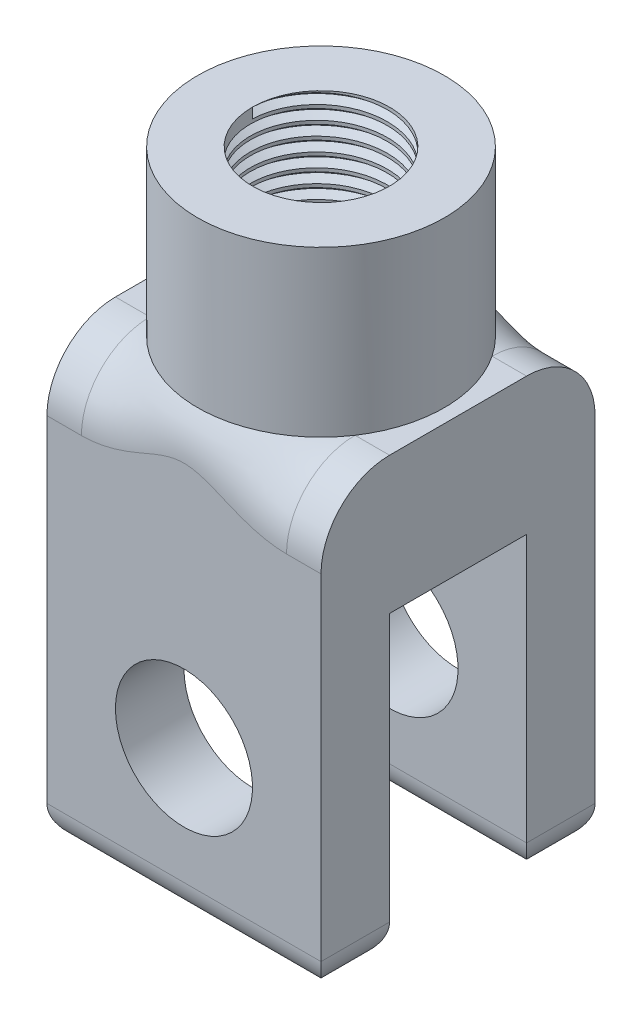
SolidWorks part; units mm, degrees
ref_plane "Front Plane" through (0, 0, 0) normal (0, 0, 1) x (1, 0, 0)
ref_plane "Top Plane" through (0, 0, 0) normal (0, 1, 0) x (1, 0, 0)
ref_plane "Right Plane" through (0, 0, 0) normal (1, 0, 0) x (0, 0, -1)
sketch "Sketch1" plane through (0, 0, 0) normal (0, 0, 1) x (1, 0, 0)
  line L1 (-10, 16) -> (10, 16)
  line L2 (-10, 16) -> (-10, -16)
  line L3 (-10, -16) -> (10, -16)
  line L4 (10, 16) -> (10, -16)
  line L5 (-10, 16) -> (10, -16) construction
  line L6 (-10, -16) -> (10, 16) construction
  point P0 (0, 0)
  dimension "D1" = 20
  dimension "D2" = 32
extrude "Boss-Extrude1" add sketch "Sketch1" along normal blind 20
sketch "Sketch2" plane through (0, 16, 0) normal (0, 1, 0) x (1, 0, 0)
  line L0 (0, 0) -> (0, -20) construction
  line L1 (10, -20) -> (-10, -20) construction
  line L2 (-10, -10) -> (10, -10) construction
  line L3 (-10, -20) -> (-10, 0) construction
  line L4 (10, -20) -> (10, 0) construction
  circle A0 centre (0, -10) radius 9
  dimension "D1" = 18
extrude "Boss-Extrude2" add sketch "Sketch2" along normal blind 12
fillet "Fillet3" radius 5 2 edges at (0, 16, 20) (0, 16, 0)
sketch "Sketch3" plane through (-10, 0, 0) normal (-1, 0, 0) x (0, 0, 1)
  line L0 (20, -16) -> (0, -16) construction
  line L1 (5, -38) -> (15, -38)
  line L2 (5, -38) -> (5, 6)
  line L3 (5, 6) -> (15, 6)
  line L4 (15, -38) -> (15, 6)
  line L5 (5, -38) -> (15, 6) construction
  line L6 (5, 6) -> (15, -38) construction
  point P0 (10, -16)
  dimension "D1" = 10
  dimension "D2" = 44
extrude "Cut-Extrude1" cut sketch "Sketch3" against normal blind 20
fillet "Fillet4" radius 2.5 8 edges at (0, -16, 20) (-10, -16, 17.5) (0, -16, 0) (-10, -16, 2.5) (0, -16, 15) (0, -16, 5) (10, -16, 17.5) (10, -16, 2.5)
sketch "Sketch4" plane through (0, 0, 0) normal (0, 0, -1) x (-1, 0, 0)
  line L0 (0, 0) -> (0, -13.5) construction
  line L1 (-10, -13.5) -> (10, -13.5) construction
  line L2 (-7.5, -16) -> (7.5, -16) construction
  circle A0 centre (0, -5) radius 5
  dimension "D1" = 10
  dimension "D2" = 11
extrude "Cut-Extrude2" cut sketch "Sketch4" against normal blind 20
sketch "Sketch5" plane through (0, 28, 0) normal (0, 1, 0) x (1, 0, 0)
  line L0 (0, -1) -> (0, -19) construction
  arc A0 (7.4833, -5) -> (-7.4833, -5) centre (0, -10) ccw construction
  arc A1 (-7.4833, -15) -> (7.4833, -15) centre (0, -10) ccw construction
  circle A2 centre (0, -10) radius 5
  dimension "D1" = 10
extrude "Cut-Extrude3" cut sketch "Sketch5" against normal blind 22
thread "Thread1" pitch 1 start angle 0, offset 0, length 22, pitch 1, diameter 10
ref_plane "Plane1" through (-5, 28, 10) normal (0, 0, 1) x (-1, 0, 0)
sketch "Thread Profile1" plane through (-5, 28, 10) normal (0, 0, 1) x (-1, 0, 0)
  line L0 (0, 0) -> (0, 1) construction
  line L1 (0, 0) -> (0.5413, 0.3125)
  line L2 (0.5413, 0.3125) -> (0.5413, 0.4375)
  line L3 (0.5413, 0.4375) -> (0, 0.75)
  line L4 (0.5413, 0.375) -> (0, 0.375) construction
  line L11 (0, 0) -> (0, 0.75)
  point P2 (0, 0)
  dimension "Pitch" = 1
  dimension "Profile_Angle" = 60
  dimension "Profile_Land" = 0.125
  dimension "Profile_Height" = 0.5413
